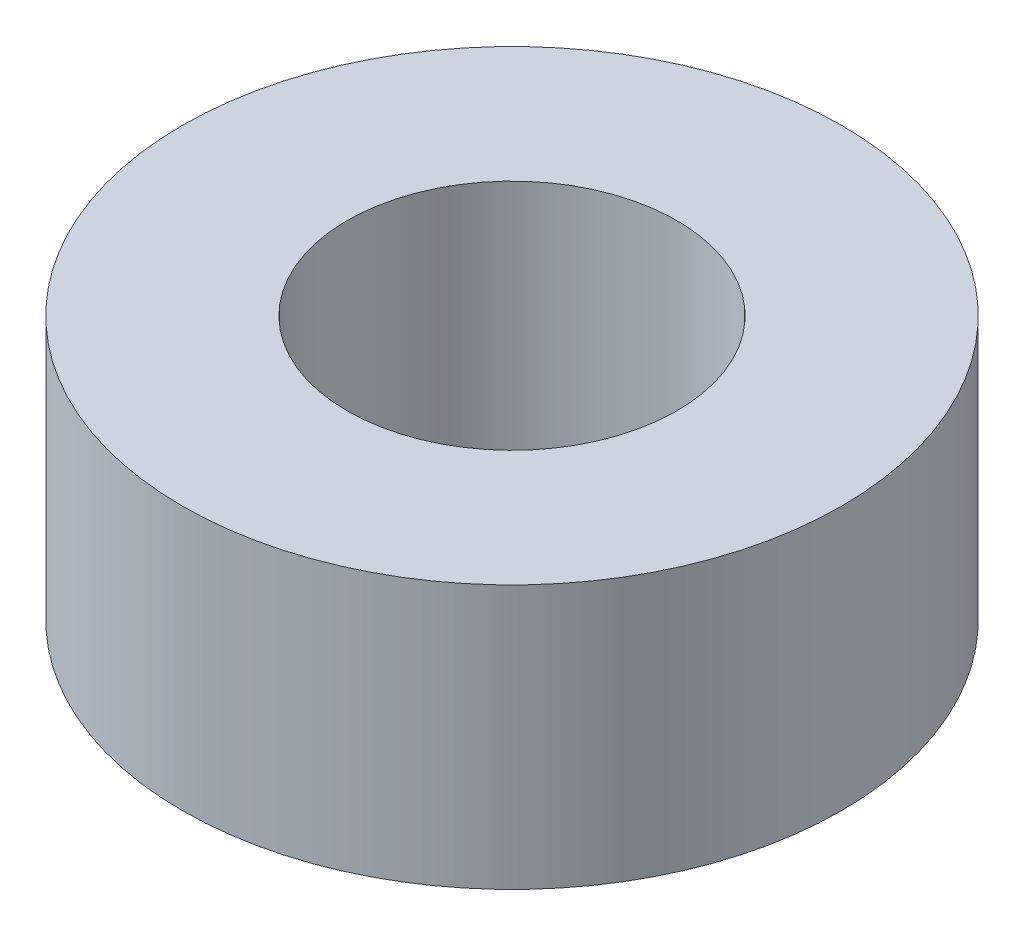
SolidWorks part; units mm, degrees
ref_plane "Front Plane" through (0, 0, 0) normal (0, 0, 1) x (1, 0, 0)
ref_plane "Top Plane" through (0, 0, 0) normal (0, 1, 0) x (1, 0, 0)
ref_plane "Right Plane" through (0, 0, 0) normal (1, 0, 0) x (0, 0, -1)
sketch "Sketch1" plane through (0, 0, 0) normal (0, 1, 0) x (1, 0, 0)
  circle A0 centre (0, 0) radius 20
  dimension "FLANGE_OD" = 40
extrude "Boss-Extrude1" add sketch "Sketch1" along normal blind 16
sketch "Sketch2" plane through (0, 0, 0) normal (0, 1, 0) x (1, 0, 0)
  circle A0 centre (0, 0) radius 10
  dimension "BORE_D" = 20
extrude "Cut-Extrude1" cut sketch "Sketch2" along normal through all
sketch "Sketch3" plane through (0, 16, 0) normal (0, 1, 0) x (1, 0, 0)
  circle A0 centre (0, 0) radius 6.6594 construction
  circle A1 centre (-6.6594, 0) radius 1.755
  dimension "BOLT_D" = 3.5101
  dimension "BOLT_PCD" = 13.3188
extrude "Cut-Extrude2" cut sketch "Sketch3" against normal blind 13.1153 rebuild error yes
pattern_circular "CirPattern1" count 3 over 360 rebuild error yes
